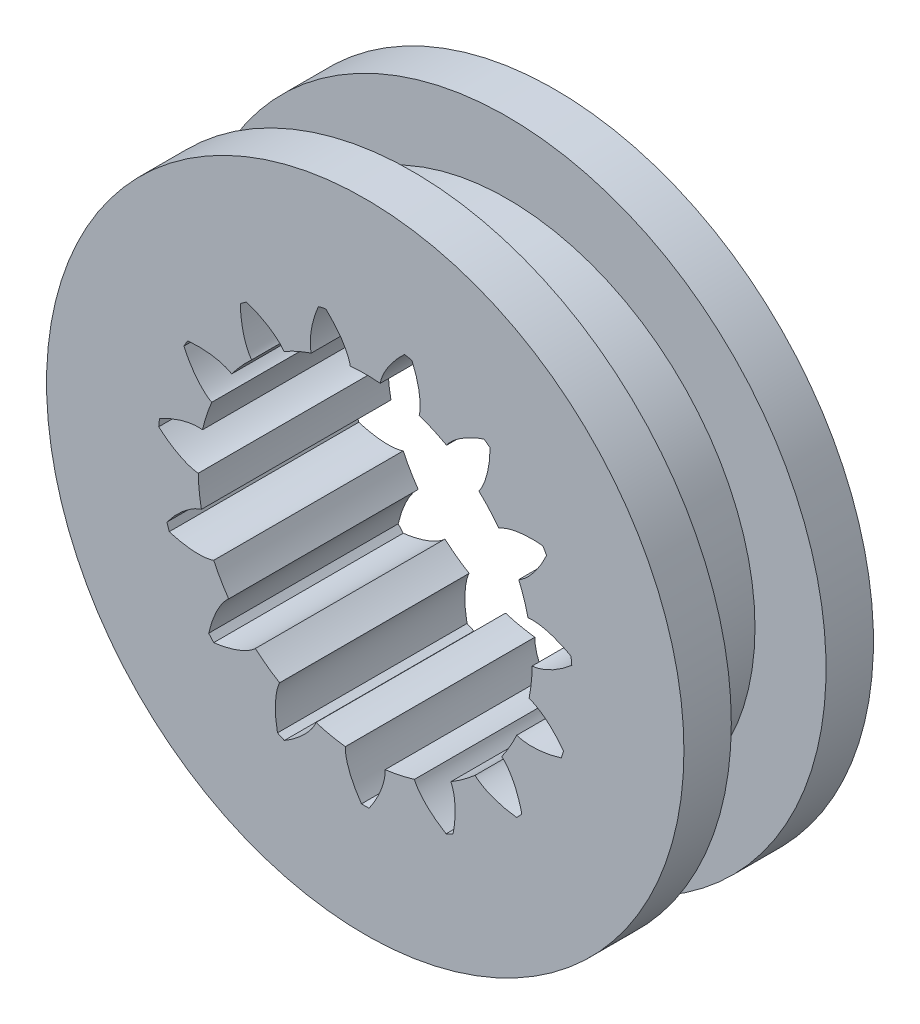
SolidWorks part; units mm, degrees
ref_plane "前视基准面" through (0, 0, 0) normal (0, 0, 1) x (1, 0, 0)
ref_plane "上视基准面" through (0, 0, 0) normal (0, 1, 0) x (1, 0, 0)
ref_plane "右视基准面" through (0, 0, 0) normal (1, 0, 0) x (0, 0, -1)
sketch "草图1" plane through (0, 0, 0) normal (0, 0, 1) x (1, 0, 0)
  circle A0 centre (0, 0) radius 4.375
  circle A1 centre (0, 0) radius 5.2262
extrude "凸台-拉伸1" add sketch "草图1" along normal blind 4
ref_axis "基准轴1" through (0, 0, 4) along (0, 0, -1)
sketch "草图2" plane through (0, 0, 0) normal (0, 0, 1) x (1, 0, 0)
  line L0 (0, 0) -> (0, 3.5238) construction
  arc A0 (0.3161, 3.5096) -> (-0.3161, 3.5096) centre (0, 0) ccw
  arc A1 (1.0078, 4.4442) -> (-1.0078, 4.4442) centre (0, 0) ccw
  spline S0 degree 3 poles (0.3161, 3.5096) (0.3175, 3.5211) (0.3204, 3.5358) (0.3249, 3.5543) (0.328, 3.5659) (0.3317, 3.5788) (0.3361, 3.5929) (0.3412, 3.6083) (0.3471, 3.6249) (0.3538, 3.6427) (0.3614, 3.6617) (0.3699, 3.6818) (0.3794, 3.703) (0.3899, 3.7254) (0.4015, 3.7487) (0.4142, 3.7731) (0.428, 3.7985) (0.4431, 3.8248) (0.4594, 3.852) (0.477, 3.88) (0.4959, 3.9089) (0.5162, 3.9386) (0.5379, 3.969) (0.5611, 4.0001) (0.5857, 4.0318) (0.6118, 4.0642) (0.6395, 4.097) (0.6688, 4.1304) (0.6997, 4.1643) (0.7322, 4.1985) (0.7664, 4.2331) (0.8023, 4.2679) (0.84, 4.303) (0.8793, 4.3383) (0.9349, 4.3861) (0.9781, 4.4212) (1.0078, 4.4442) knots 0 0 0 0 0.029141 0.038065 0.048178 0.059481 0.071973 0.085656 0.100528 0.11659 0.133842 0.152283 0.171915 0.192736 0.214747 0.237947 0.262338 0.287918 0.314688 0.342648 0.371797 0.402137 0.433666 0.466385 0.500293 0.535392 0.57168 0.609158 0.647826 0.687683 0.728731 0.770968 0.814395 0.859011 0.904818 1 1 1 1
  spline S1 degree 3 poles (-0.3161, 3.5096) (-0.3175, 3.5211) (-0.3204, 3.5358) (-0.3249, 3.5543) (-0.328, 3.5659) (-0.3317, 3.5788) (-0.3361, 3.5929) (-0.3412, 3.6083) (-0.3471, 3.6249) (-0.3538, 3.6427) (-0.3614, 3.6617) (-0.3699, 3.6818) (-0.3794, 3.703) (-0.3899, 3.7254) (-0.4015, 3.7487) (-0.4142, 3.7731) (-0.428, 3.7985) (-0.4431, 3.8248) (-0.4594, 3.852) (-0.477, 3.88) (-0.4959, 3.9089) (-0.5162, 3.9386) (-0.5379, 3.969) (-0.5611, 4.0001) (-0.5857, 4.0318) (-0.6118, 4.0642) (-0.6395, 4.097) (-0.6688, 4.1304) (-0.6997, 4.1643) (-0.7322, 4.1985) (-0.7664, 4.2331) (-0.8023, 4.2679) (-0.84, 4.303) (-0.8793, 4.3383) (-0.9349, 4.3861) (-0.9781, 4.4212) (-1.0078, 4.4442) knots 0 0 0 0 0.029141 0.038065 0.048178 0.059481 0.071973 0.085656 0.100528 0.11659 0.133842 0.152283 0.171915 0.192736 0.214747 0.237947 0.262338 0.287918 0.314688 0.342648 0.371797 0.402137 0.433666 0.466385 0.500293 0.535392 0.57168 0.609158 0.647826 0.687683 0.728731 0.770968 0.814395 0.859011 0.904818 1 1 1 1
extrude "凸台-拉伸2" add sketch "草图2" along normal blind 4
pattern_circular "阵列(圆周)1" count 15 every 24 about axis through (0, 0, 4) along (0, 0, -1) of "凸台-拉伸2"
sketch "草图3" plane through (0, 0, 0) normal (0, 0, 1) x (1, 0, 0)
  circle A0 centre (0, 0) radius 3.75 construction
  dimension "Dn" = 7.5
sketch "草图6" plane through (0, 0, 4) normal (0, 0, 1) x (1, 0, 0)
  circle A0 centre (0, 0) radius 6.7262
  circle A1 centre (0, 0) radius 5.2262 construction
  circle A2 centre (0, 0) radius 5.2262
  dimension "D1" = 1.5
extrude "凸台-拉伸3" add sketch "草图6" against normal blind 1
sketch "草图7" plane through (0, 0, 0) normal (0, 0, -1) x (-1, 0, 0)
  circle A0 centre (0, 0) radius 6.7262
  circle A1 centre (0, 0) radius 6.7262 construction
  circle A2 centre (0, 0) radius 5.2262 construction
  circle A3 centre (0, 0) radius 5.2262
extrude "凸台-拉伸4" add sketch "草图7" against normal blind 1
